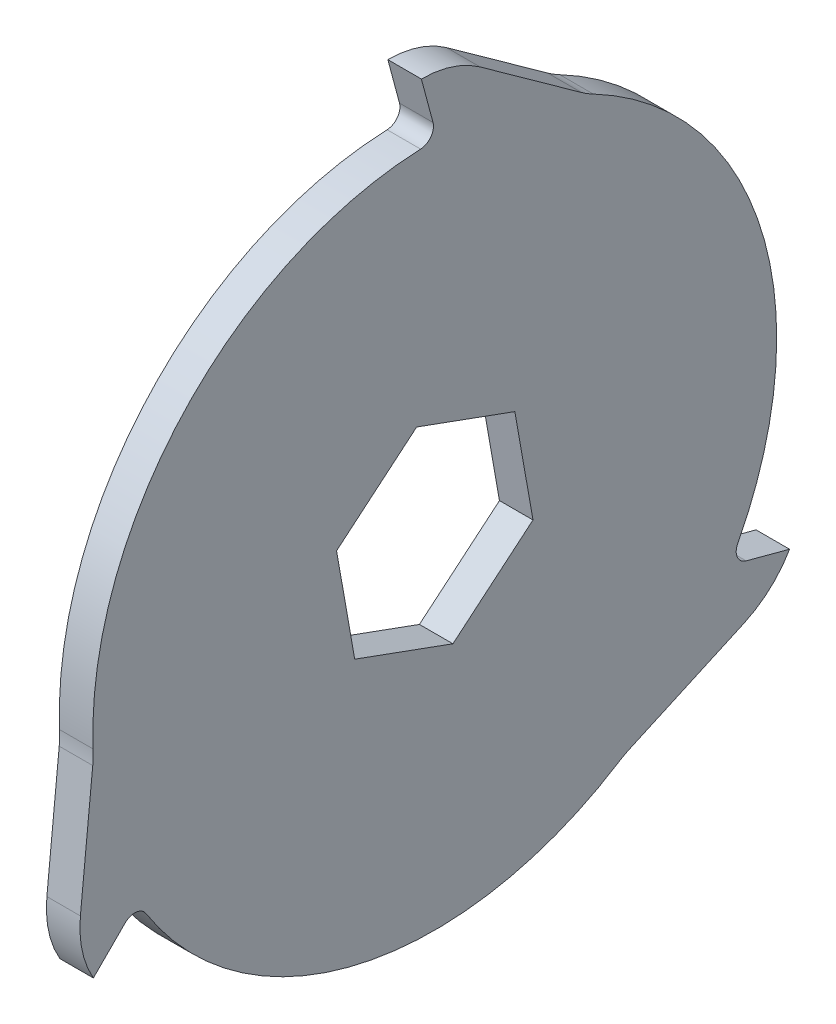
SolidWorks part; units mm, degrees
note: '?' marks a value the reader was unsure of.
material "1.0037 (S235JR)"
ref_plane "Alzado" through (0, 0, 0) normal (0, 0, 1) x (1, 0, 0)
ref_plane "Planta" through (0, 0, 0) normal (0, 1, 0) x (1, 0, 0)
ref_plane "Vista lateral" through (0, 0, 0) normal (1, 0, 0) x (0, 0, -1)
sketch "Sketch1" plane through (0, 0, 0) normal (1, 0, 0) x (0, 0, -1)
  line L0 (-56.6126, 0) -> (65.57, 0) construction
  line L1 (11.9415, 10.0201) -> (-2.7069, 15.3516)
  line L2 (-2.7069, 15.3516) -> (-14.6484, 5.3316)
  line L3 (-14.6484, 5.3316) -> (-11.9415, -10.0201)
  line L4 (-11.9415, -10.0201) -> (2.7069, -15.3516)
  line L5 (2.7069, -15.3516) -> (14.6484, -5.3316)
  line L6 (14.6484, -5.3316) -> (11.9415, 10.0201)
  circle A0 centre (0, 0) radius 13.5 construction
  circle A1 centre (0, 0) radius 51
  dimension "D2" = 102
  dimension "D1" = 27
  dimension "D3" = 20
extrude "Extrude1" add sketch "Sketch1" along normal mid plane 5
ref_axis "Axis1" through (-5.5, 0, 0) along (1, 0, 0)?
sketch "Sketch2" plane through (0, 0, 0) normal (1, 0, 0) x (0, 0, -1)
  line L0 (-2, 59.9563) -> (-0.2626, 53.4722)
  line L1 (0, 0) -> (0, 77.6328) construction
  line L2 (21.8551, 46.2915) -> (6.75, 57.1398)
  line L3 (-2.1116, 50.9563) -> (0, 0) construction
  line L4 (0, 0) -> (23.6494, 45.1852) construction
  circle A0 centre (0, 0) radius 51 construction
  arc A1 (-2, 59.9563) -> (6.75, 57.1398) centre (-2, 44.9563) cw
  arc A3 (23.6494, 45.1852) -> (-2.1116, 50.9563) centre (0, 0) ccw
  arc A4 (-0.2626, 53.4722) -> (-2.1116, 50.9563) centre (-2.1944, 52.9546) cw
  arc A5 (21.8551, 46.2915) -> (23.6494, 45.1852) centre (30.6051, 58.475) ccw
  point P13 (-2, 59.9563)
  dimension "D2" = 15
  dimension "D4" = 2
  dimension "D3" = 9
  dimension "D7" = 15
  dimension "D1" = 15
  dimension "D5" = 2
  dimension "D6" = 30
extrude "Extrude2" add sketch "Sketch2" against normal mid plane 5
fillet "Fillet1" [suppressed] radius 0.6
pattern_circular "CirPattern1" count 3 over 360 about axis through (0, 0, 0) along (1, 0, 0) of "Extrude2", "Fillet1"
sketch "Sketch3" [suppressed] plane through (3, 0, 0) normal (1, 0, 0) x (0, 0, -1)
  circle A0 centre (0, 0) radius 67.9496 construction
  dimension "D1" = 135.8992
hole_wizard "Ø2.5 (2.5) Diameter Hole1" [suppressed] positions "Sketch4" profile "Sketch5" hole size "Ø2.5" standard "ISO"
sketch "Sketch4" plane through (2.5, 0, 0) normal (1, 0, 0) x (0, 0, -1)
  point P0 (-7.7942, 13.5)
  point P3 (7.7942, 13.5)
  point P6 (15.5885, 0)
  point P9 (7.7942, -13.5)
  point P12 (-7.7942, -13.5)
  point P15 (-15.5885, 0)
sketch "Sketch5" plane through (2.5, 13.5, 7.7942) normal (0, 1, 0) x (0, 0, -1)
  line L0 (0, 0) -> (0, 5)
  line L1 (0, 5) -> (1.25, 5)
  line L2 (1.25, 5) -> (1.25, 0)
  line L5 (1.25, 0) -> (0, 0)
  line L11 (0, -6.35) -> (0, 107.95) construction
  dimension "Diámetro de taladro hasta el siguiente" = 2.5
  dimension "Profundidad de taladro hasta el siguiente" = 5
hole_wizard "Ø3.0 (3) Diameter Hole1" [suppressed] positions "Sketch6" profile "Sketch7" hole size "Ø3.0" standard "ISO"
sketch "Sketch6" plane through (2.5, 0, 0) normal (1, 0, 0) x (0, 0, -1)
  line L0 (6.5442, 13.5) -> (-6.5442, 13.5) construction
  point P19 (0, 13.5)
sketch "Sketch7" plane through (2.5, 13.5, 0) normal (0, 1, 0) x (0, 0, -1)
  line L0 (0, 0) -> (0, 5)
  line L1 (0, 5) -> (1.5, 5)
  line L2 (1.5, 5) -> (1.5, 0)
  line L5 (1.5, 0) -> (0, 0)
  line L11 (0, -6.35) -> (0, 107.95) construction
  dimension "Diámetro de taladro hasta el siguiente" = 3
  dimension "Profundidad de taladro hasta el siguiente" = 5
equation "\"D1@Extrude2\"=\"D1@Extrude1\""
